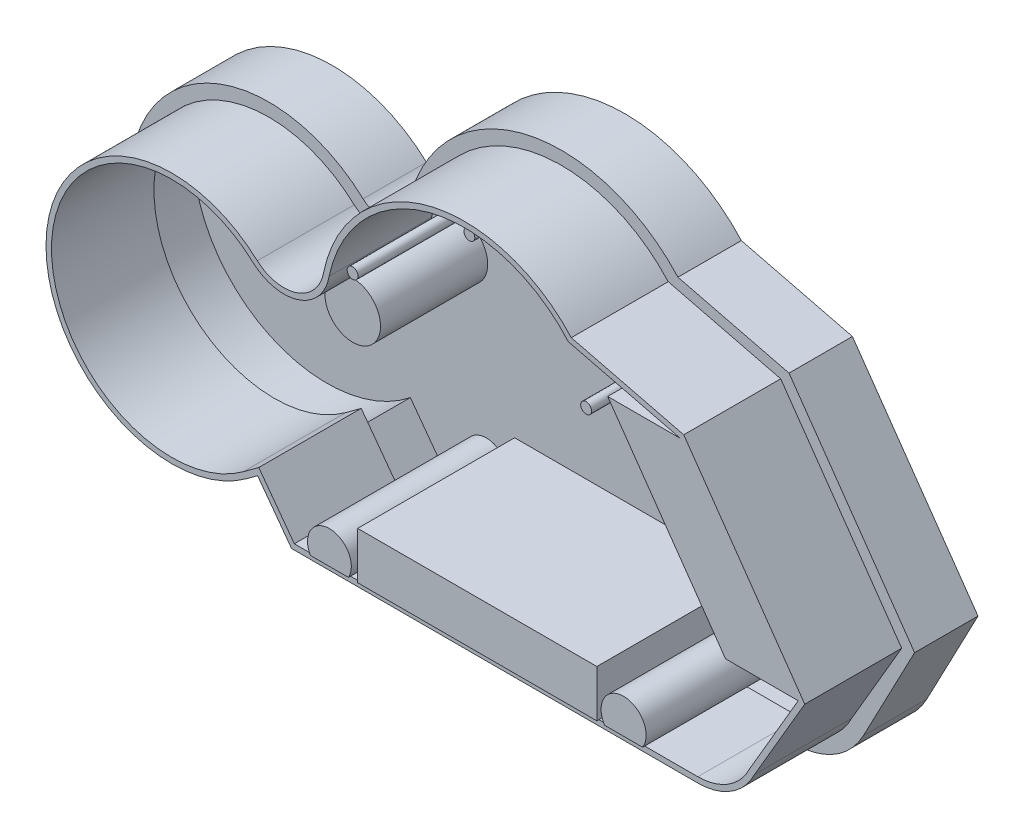
SolidWorks part; units mm, degrees
ref_plane "Front Plane" through (0, 0, 0) normal (0, 0, 1) x (1, 0, 0)
ref_plane "Top Plane" through (0, 0, 0) normal (0, 1, 0) x (1, 0, 0)
ref_plane "Right Plane" through (0, 0, 0) normal (1, 0, 0) x (0, 0, -1)
sketch "Sketch1" plane through (0, 0, 0) normal (0, 0, 1) x (1, 0, 0)
  line L1 (0, 0) -> (300, 0)
  line L2 (0, 0) -> (0, -152)
  line L3 (0, -152) -> (300, -152)
  line L4 (300, 0) -> (300, -152)
  dimension "D1" = 300
  dimension "D2" = 152
extrude "Boss-Extrude1" add sketch "Sketch1" along normal blind 61.3
sketch "Sketch2" plane through (0, 0, 61.3) normal (0, 0, 1) x (1, 0, 0)
  line L0 (0, 0) -> (0, -152) construction
  line L1 (300, 0) -> (0, 0) construction
  line L2 (251.9917, -30.2937) -> (209.5237, -19.7801)
  line L3 (0, -152) -> (300, -152) construction
  line L4 (300, -152) -> (300, 0) construction
  line L5 (224.1817, -30.2937) -> (272.19, -98.8567)
  line L6 (272.19, -98.8567) -> (300, -98.8567)
  line L7 (300, -98.8567) -> (251.9917, -30.2937)
  line L8 (251.9917, -30.2937) -> (224.1817, -30.2937)
  line L9 (103.48, -152) -> (96.53, -152)
  line L10 (300, -98.8567) -> (280.4136, -136.1519)
  line L11 (211.19, -152) -> (119.74, -152)
  line L12 (211.19, -152) -> (211.19, -134)
  line L13 (211.19, -134) -> (119.74, -134)
  line L14 (119.74, -152) -> (119.74, -134)
  line L15 (96.53, -152) -> (81.7043, -131.8705)
  line L16 (84.6693, -135.8961) -> (96.53, -152)
  line L17 (118, -152) -> (212.93, -152)
  line L18 (227.45, -152) -> (254.19, -152)
  line L19 (280.4136, -136.1519) -> (300, -98.8567)
  line L20 (300, -98.8567) -> (251.9917, -30.2937)
  line L21 (209.5237, -19.7801) -> (251.9917, -30.2937)
  circle A1 centre (165, -60) radius 55
  circle A3 centre (53.15, -93.1009) radius 48.15
  circle A4 centre (254.19, -122.38) radius 29.62
  circle A5 centre (53.15, -93.1009) radius 53.1497 construction
  circle A6 centre (165, -60) radius 60 construction
  arc A7 (106.2766, -47.6888) -> (89.1669, -54.0154) centre (96.1067, -46.4843) cw
  arc A8 (103.48, -152) -> (118, -152) centre (110.74, -149.0765) cw
  arc A9 (212.93, -152) -> (227.45, -152) centre (220.19, -149.0765) cw
  arc A10 (89.1669, -54.0154) -> (84.6693, -135.8961) centre (53.15, -93.1009) ccw
  arc A11 (103.48, -152) -> (118, -152) centre (110.74, -149.0765) cw
  arc A12 (254.19, -152) -> (280.4136, -136.1519) centre (254.19, -122.38) ccw
  arc A13 (106.2766, -47.6888) -> (209.5237, -19.7801) centre (165, -60) cw
  point P32 (110.74, -141.25)
  point P36 (220.19, -141.25)
  line M4 (0, 0) -> (0, -152)
  line M5 (0, -152) -> (300, -152)
  line M6 (300, -152) -> (300, 0)
  line M7 (300, 0) -> (0, 0)
  dimension "D1" = 96.3
  dimension "D2" = 110
  dimension "D3" = 59.24
  dimension "D4" = 45.81
  dimension "D6" = 27.81
  dimension "D12" = 120
  dimension "D15" = 43
  dimension "D5" = 165
  dimension "D7" = 125
  dimension "D8" = 83.7
  dimension "D9" = 43.75
  dimension "D10" = 53.15
  dimension "D11" = 60
  dimension "D13" = 18
  dimension "D14" = 91.45
  dimension "D16" = 14.52
  dimension "D17" = 10.75
  dimension "D18" = 9
  dimension "D19" = 14.52
  dimension "D20" = 10.75
  dimension "D21" = 9
  dimension "D22" = 6.95
  dimension "D23" = 25
extrude "Cut-Extrude1" cut sketch "Sketch2" against normal through all contours A7 A13 L15 A10 M7 M4 M5 | A13 L2 L7 M7 M6 | A4 L10 M5 M6 region at (263.7567, -28.0884, 61.3) region at (289.3143, -135.2493, 61.3) region at (125.7616, -11.6824, 61.3)
sketch "Sketch3" plane through (0, 0, 61.3) normal (0, 0, 1) x (1, 0, 0)
  line L2 (205.8134, -23.1318) -> (248.8051, -33.775)
  line L5 (251.9917, -30.2937) -> (209.5237, -19.7801) construction
  line L6 (248.8051, -33.775) -> (295.0698, -99.8479)
  line L8 (300, -98.8567) -> (251.9917, -30.2937) construction
  line L9 (275.8484, -132.7662) -> (295.0698, -99.8479)
  line L10 (254.19, -146.4) -> (98.8799, -146.4)
  line L12 (81.7043, -131.8705) -> (85.9018, -128.7789)
  line L13 (85.9018, -128.7789) -> (98.8799, -146.4)
  line L14 (96.53, -152) -> (84.6693, -135.8961) construction
  arc A2 (85.7788, -57.6921) -> (81.7043, -131.8705) centre (53.15, -93.1009) ccw
  arc A3 (89.1669, -54.0154) -> (84.6693, -135.8961) centre (53.15, -93.1009) ccw
  arc A4 (89.1669, -54.0154) -> (106.2766, -47.6888) centre (96.1067, -46.4843) ccw
  arc A5 (209.5237, -19.7801) -> (105.9779, -49.2116) centre (165, -60) ccw
  arc A6 (205.8134, -23.1318) -> (111.1702, -48.7147) centre (165, -60) ccw
  arc A7 (85.7788, -57.6921) -> (111.1702, -48.7147) centre (95.9632, -46.1005) ccw
  arc A8 (89.1669, -54.0154) -> (106.2766, -47.6888) centre (96.1067, -46.4843) ccw
  arc A9 (254.19, -146.4) -> (275.8484, -132.7662) centre (254.19, -122.38) ccw
  line M7 (280.4136, -136.1519) -> (300, -98.8567)
  line M8 (300, -98.8567) -> (251.9917, -30.2937)
  line M9 (251.9917, -30.2937) -> (209.5237, -19.7801)
  arc M10 (209.5237, -19.7801) -> (106.2766, -47.6888) centre (165, -60) ccw
  arc M11 (106.2766, -47.6888) -> (89.1669, -54.0154) centre (96.1067, -46.4843) cw
  arc M12 (89.1669, -54.0154) -> (84.6693, -135.8961) centre (53.15, -93.1009) ccw
  line M13 (84.6693, -135.8961) -> (96.53, -152)
  line M14 (96.53, -152) -> (254.19, -152)
  arc M15 (254.19, -152) -> (280.4136, -136.1519) centre (254.19, -122.38) ccw
  dimension "D1" = 110
  dimension "D2" = 96.3
  dimension "D3" = 48.04
extrude "Cut-Extrude2" cut sketch "Sketch3" against normal blind 37.06 contours A4 A9 L10 L13 L12 A2 A7 A6 L2 L6 L9 M15 M7 M8 M9 M10 M11 M12 M13 M14 region at (99.8445, -59.5649, 61.3)
shell "Shell2" thickness 2.1 removed face at (166.1248, -92.6608, 61.3)
sketch "Sketch9" plane through (0, 0, 61.3) normal (0, 0, 1) x (1, 0, 0)
  line L0 (247.5364, -35.6243) -> (219.7264, -35.6243)
  line L1 (219.7264, -35.6243) -> (264.7681, -99.9506)
  line L2 (264.7681, -99.9506) -> (292.5781, -99.9506)
  line L3 (292.5781, -99.9506) -> (248.1355, -36.4799)
  line L4 (247.5364, -35.6243) -> (292.5781, -99.9506) construction
  line L11 (99.9414, -144.3) -> (254.19, -144.3)
  line L12 (86.3473, -125.8427) -> (99.9414, -144.3)
  line L13 (80.4589, -130.1796) -> (86.3473, -125.8427)
  line L14 (247.5364, -35.6243) -> (204.6788, -25.0143)
  line L15 (292.5781, -99.9506) -> (247.5364, -35.6243)
  line L16 (273.9908, -131.7828) -> (292.5781, -99.9506)
  line L21 (248.1355, -36.4799) -> (247.5364, -35.6243)
  arc A4 (254.19, -144.3) -> (273.9908, -131.7828) centre (254.19, -122.38) ccw
  arc A5 (84.3733, -59.2526) -> (80.4589, -130.1796) centre (53.15, -93.1009) ccw
  arc A6 (84.3733, -59.2526) -> (113.2331, -49.1098) centre (95.9632, -46.1005) ccw
  arc A7 (204.6788, -25.0143) -> (113.2331, -49.1098) centre (165, -60) ccw
  dimension "D1" = 27.81
  dimension "D2" = 125
  dimension "D3" = 0
extrude "Boss-Extrude3" add sketch "Sketch9" against normal blind 59.06
sketch "Sketch10" plane through (0, 0, 2.1) normal (0, 0, 1) x (1, 0, 0)
  circle A0 centre (118, -47.7419) radius 2.075
  circle A1 centre (207.29, -47.7419) radius 2.075
  circle A2 centre (162.6504, -12.6338) radius 2.075
  arc A4 (204.6788, -25.0143) -> (113.2331, -49.1098) centre (165, -60) ccw construction
  dimension "D1" = 4.15
  dimension "D2" = 4.15
  dimension "D3" = 4.15
  dimension "D5" = 89.29
  dimension "D4" = 56.8
  dimension "D6" = 47
extrude "Boss-Extrude4" add sketch "Sketch10" along normal blind 55
sketch "Sketch11" plane through (0, 0, 2.1) normal (0, 0, 1) x (1, 0, 0)
  circle A0 centre (104.051, -74.0143) radius 10.625
  dimension "D1" = 21.25
extrude "Boss-Extrude7" add sketch "Sketch11" along normal blind 41 contours A0
sketch "Sketch12" plane through (0, 0, 2.1) normal (0, 0, 1) x (1, 0, 0)
  line L0 (124.9414, -144.3) -> (124.9414, -126.3)
  line L1 (254.19, -144.3) -> (99.9414, -144.3) construction
  line L2 (124.9414, -126.3) -> (216.3914, -126.3)
  line L3 (216.3914, -126.3) -> (216.3914, -144.3)
  line L4 (216.3914, -144.3) -> (124.9414, -144.3)
  line L5 (106.8914, -144.3) -> (121.4114, -144.3)
  line L6 (219.3504, -144.3) -> (233.8704, -144.3)
  arc A0 (106.8914, -144.3) -> (121.4114, -144.3) centre (114.1514, -140.1304) cw
  arc A1 (219.3504, -144.3) -> (233.8704, -144.3) centre (226.6104, -139.6617) cw
  dimension "D5" = 6.95
  dimension "D1" = 91.45
  dimension "D2" = 18
  dimension "D3" = 25
  dimension "D4" = 14.52
  dimension "D6" = 14.52
extrude "Boss-Extrude8" add sketch "Sketch12" along normal blind 60
